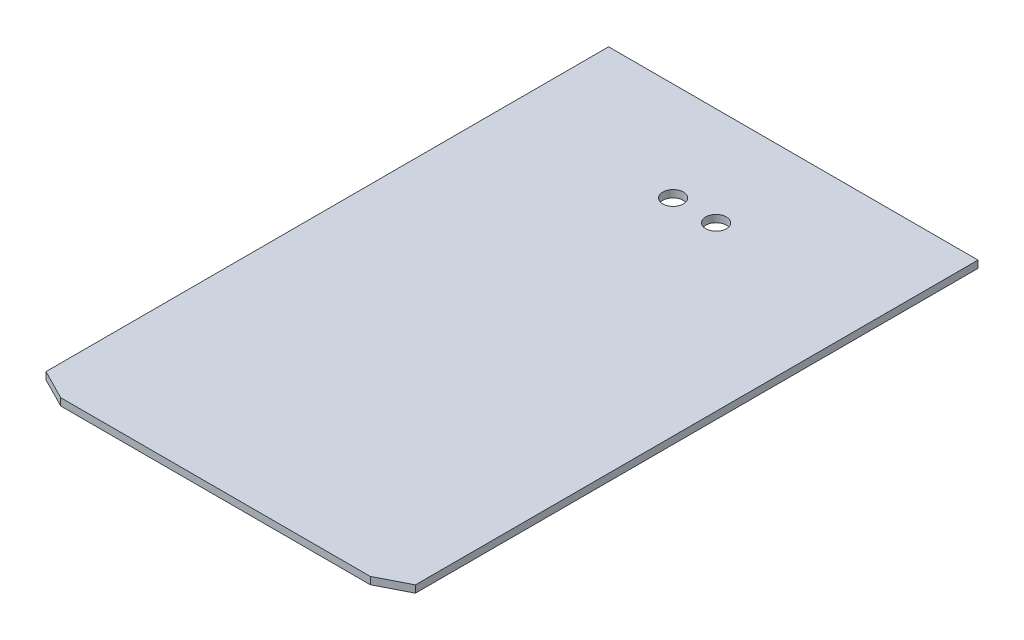
SolidWorks part; units mm, degrees
ref_plane "Front Plane" through (0, 0, 0) normal (0, 0, 1) x (1, 0, 0)
ref_plane "Top Plane" through (0, 0, 0) normal (0, 1, 0) x (1, 0, 0)
ref_plane "Right Plane" through (0, 0, 0) normal (1, 0, 0) x (0, 0, -1)
sketch "Sketch1" plane through (0, 0, 0) normal (0, 1, 0) x (1, 0, 0)
  line L0 (-21.4, 26.5) -> (-20.9, 26.5)
  line L3 (-21.4, 29.5) -> (-21.4, 26.5)
  line L11 (-20.4, 30.5) -> (20.4, 30.5)
  line L17 (0, 30.5) -> (0, -30.5) construction
  line L21 (21.4, 29.5) -> (21.4, 26.5)
  line L22 (21.4, 26.5) -> (20.9, 26.5)
  line L23 (-20.9, 26.5) -> (-20.9, -23.5)
  line L24 (-20.9, -23.5) -> (20.9, -23.5) construction
  line L25 (20.9, -23.5) -> (20.9, 26.5)
  line L26 (-15, -26.5) -> (15, -26.5)
  line L29 (-20.9, -23.5) -> (-15, -26.5)
  line L30 (15, -26.5) -> (20.9, -23.5)
  line L31 (-21.4, 29.5) -> (-20.4, 30.5)
  line L32 (21.4, 29.5) -> (20.4, 30.5)
  circle A6 centre (-19.9444, 29.1814) radius 1
  circle A8 centre (19.9444, 29.1814) radius 1
  point P17 (0, 0)
  point P19 (0, -26.5)
  dimension "D6" = 30.5
  dimension "D9" = 40.8
  dimension "D3" = 29.1814
  dimension "D5" = 45
  dimension "D2" = 19.9444
  dimension "D12" = 2
  dimension "D4" = 50
  dimension "D7" = 35.9
  dimension "D8" = 3
  dimension "D10" = 26.5
  dimension "D11" = 20.9
  dimension "D13" = 0.5
extrude "Boss-Extrude1" add sketch "Sketch1" along normal blind 0.7
sketch "Sketch2" plane through (0, 0.7, 0) normal (0, 1, 0) x (1, 0, 0)
  line L0 (-2.0845, 19.9345) -> (2.0845, 19.9345) construction
  line L1 (0, 19.9345) -> (0, 0) construction
  circle A0 centre (-2.0845, 19.9345) radius 1
  circle A1 centre (2.0845, 19.9345) radius 1
  point P6 (0, 0)
  dimension "D2" = 2
  dimension "D1" = 4.1691
  dimension "D3" = 19.9345
extrude "Cut-Extrude1" cut sketch "Sketch2" against normal blind 4.5
sketch "Sketch4" plane through (0, 0.7, 0) normal (0, 1, 0) x (1, 0, 0)
  line L5 (-15, -26.5) -> (15, -26.5) construction
  line L15 (-17.9, 29.5) -> (-17.9, -26.5)
  line L16 (-17.9, -26.5) -> (17.9, -26.5)
  line L17 (17.9, 29.5) -> (17.9, -26.5)
  line L18 (-17.9, 29.5) -> (17.9, -26.5) construction
  line L19 (-17.9, -26.5) -> (17.9, 29.5) construction
  line L20 (0, 29.5) -> (0, -26.5) construction
  line L21 (-17.9, 29.5) -> (0, 29.5)
  line L22 (0, 29.5) -> (17.9, 29.5)
  line L23 (-20.9, 26.5) -> (-20.9, -23.5) construction
  line L24 (20.4, 30.5) -> (-20.4, 30.5) construction
  point P4 (0, 1.5)
  point P11 (0.3413, 23.162)
  dimension "D1" = 3
  dimension "D2" = 1
extrude "Cut-Extrude2" cut sketch "Sketch4" against normal blind 10 flip side to cut
